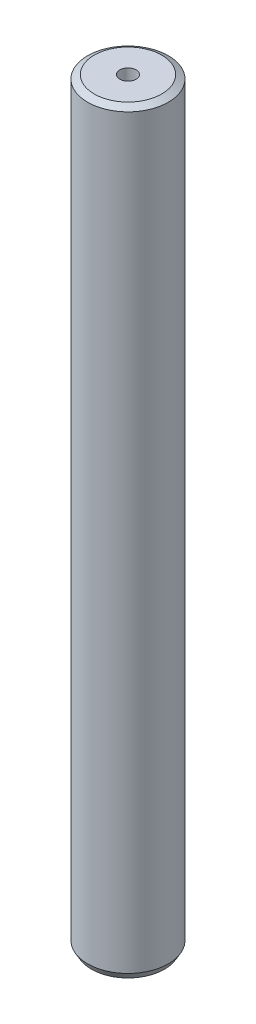
SolidWorks part; units mm, degrees
ref_plane "Front Plane" through (0, 0, 0) normal (0, 0, 1) x (1, 0, 0)
ref_plane "Top Plane" through (0, 0, 0) normal (0, 1, 0) x (1, 0, 0)
ref_plane "Right Plane" through (0, 0, 0) normal (1, 0, 0) x (0, 0, -1)
sketch "Sketch1" plane through (0, 0, 0) normal (0, 1, 0) x (1, 0, 0)
  circle A0 centre (0, 0) radius 5
  dimension "SHAFT_OD" = 10
extrude "Boss-Extrude1" add sketch "Sketch1" along normal blind 93.7449
sketch "Sketch2" plane through (0, 0, 0) normal (0, 1, 0) x (1, 0, 0)
  circle A0 centre (0, 0) radius 1.0083
  dimension "BORE_D" = 2.0166
extrude "Cut-Extrude1" cut sketch "Sketch2" along normal through all
chamfer "Chamfer1" distance 0.4733 angle 60 2 edges at (0, 93.7449, 5) (0, 0, 5) first distance on face at (0, 93.7449, 5) first distance on face at (0, 0, 1.0083)
